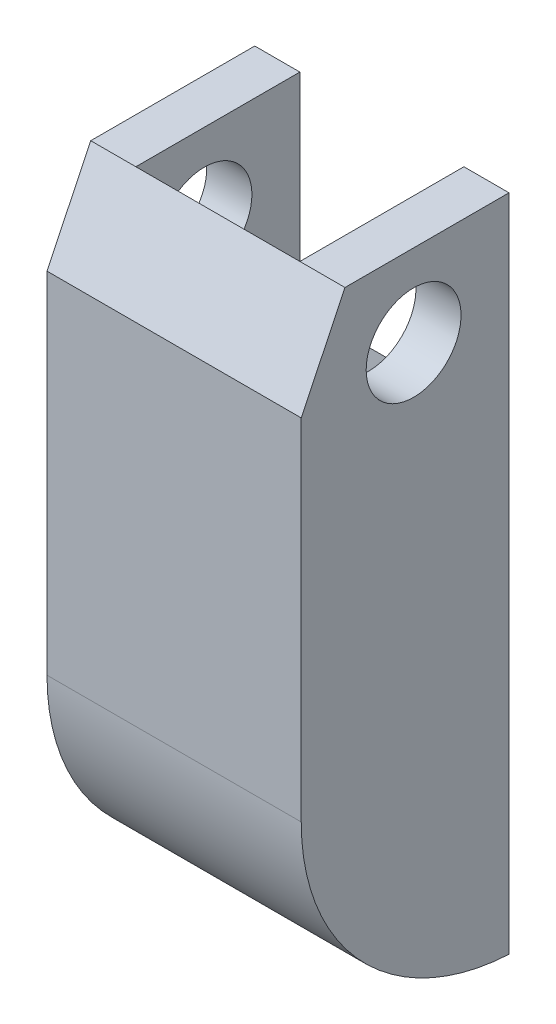
SolidWorks part; units mm, degrees
ref_plane "Front Plane" through (0, 0, 0) normal (0, 0, 1) x (1, 0, 0)
ref_plane "Top Plane" through (0, 0, 0) normal (0, 1, 0) x (1, 0, 0)
ref_plane "Right Plane" through (0, 0, 0) normal (1, 0, 0) x (0, 0, -1)
sketch "Sketch1" plane through (0, 0, 0) normal (0, 0, 1) x (1, 0, 0)
  line L1 (0, 0) -> (11.811, 0)
  line L2 (0, 0) -> (0, 45.9892)
  line L3 (0, 45.9892) -> (11.811, 45.9892)
  line L4 (11.811, 0) -> (11.811, 45.9892)
  dimension "D1" = 11.811
  dimension "D2" = 45.9892
extrude "Boss-Extrude1" add sketch "Sketch1" along normal blind 9.652 contours L2 L3 L4 L1
fillet "Fillet5" radius 4.826 1 edges at (5.9055, 45.9892, 0)
sketch "Sketch2" plane through (0, 0, 0) normal (0, 0, -1) x (-1, 0, 0)
  line L0 (0, 45.9892) -> (-11.811, 45.9892) construction
  line L1 (-9.7155, 45.9892) -> (-2.0955, 45.9892)
  line L2 (-9.7155, 45.9892) -> (-9.7155, 23.6372)
  line L3 (-9.7155, 23.6372) -> (-2.0955, 23.6372)
  line L4 (-2.0955, 45.9892) -> (-2.0955, 23.6372)
  line L5 (0, 0) -> (0, 41.1632) construction
  dimension "D1" = 22.352
  dimension "D2" = 7.62
  dimension "D3" = 2.0955
extrude "Cut-Extrude1" cut sketch "Sketch2" against normal blind 7.62
sketch "Sketch3" plane through (0, 0, 0) normal (-1, 0, 0) x (0, 0, 1)
  line L0 (7.62, 45.9892) -> (7.62, 23.6372) construction
  line L2 (7.62, 23.6372) -> (0, 23.6372) construction
  circle A0 centre (4.4323, 26.8249) radius 2.2035
  dimension "D1" = 3.1877
  dimension "D3" = 4.4069
  dimension "D2" = 3.1877
extrude "Cut-Extrude2" cut sketch "Sketch3" against normal through all and the other way through all
fillet "Fillet4" radius 4.826 1 edges at (5.9055, 45.9892, 9.652)
fillet "Fillet6" radius 10.16 1 edges at (5.9055, 0, 9.652)
sketch "Sketch4" plane through (11.811, 0, 0) normal (1, 0, 0) x (0, 0, -1)
  line L0 (-9.652, 26.4038) -> (-7.62, 30.6349)
  line L1 (-9.652, 10.1473) -> (-9.652, 41.1632) construction
  line L2 (-7.62, 30.6349) -> (0, 30.6349)
  line L3 (0, 0) -> (0, 41.1632) construction
  line L4 (-9.652, 26.4038) -> (-9.652, 45.9892)
  line L5 (-9.652, 45.9892) -> (0, 45.9892)
  line L6 (0, 45.9892) -> (0, 30.6349)
  line L7 (-0.4369, 28.7437) -> (4.2626, 18.9582) construction
  line L8 (-4.4323, 26.8249) -> (0, 26.8249) construction
  line L9 (-4.4323, 26.8249) -> (-0.4369, 28.7437) construction
  line L10 (-4.4323, 26.8249) -> (-0.4369, 24.9061) construction
  arc A0 (-4.826, 45.9892) -> (-9.652, 41.1632) centre (-4.826, 41.1632) ccw construction
  circle A1 centre (7.1247, 20.3327) radius 3.175 construction
  point P14 (-4.4323, 26.8249)
  point P22 (0, 0)
  point P23 (0, 0)
  dimension "D2" = 6.35
  dimension "D1" = 3.81
  dimension "D3" = 11.557
  dimension "D4" = 6.4922
extrude "Cut-Extrude3" cut sketch "Sketch4" against normal through all
sketch "Sketch5" plane through (9.7155, 0, 0) normal (-1, 0, 0) x (0, 0, 1)
  line L0 (5.1581, 23.6372) -> (0, 21.1601)
  line L1 (0, 21.1601) -> (0, 23.6372)
  line L2 (0, 23.6372) -> (5.1581, 23.6372)
  line L3 (4.4323, 26.8249) -> (0.4369, 24.9061) construction
  line L4 (4.4323, 26.8249) -> (7.62, 26.8249) construction
  line L5 (4.4323, 26.8249) -> (5.8123, 23.9514) construction
  line L6 (7.62, 30.6349) -> (7.62, 23.6372) construction
  line L7 (5.8123, 23.9514) -> (5.1581, 23.6372)
  line L8 (7.62, 26.8249) -> (7.62, 23.6372)
  line L9 (7.62, 23.6372) -> (5.1581, 23.6372)
  arc A0 (5.8123, 23.9514) -> (7.62, 26.8249) centre (4.4323, 26.8249) ccw
  point P2 (7.62, 26.845)
  point P13 (0, 0)
  line M4 (7.62, 23.6372) -> (7.62, 30.6349)
  line M7 (0, 23.6372) -> (7.62, 23.6372)
extrude "Cut-Extrude4" cut sketch "Sketch5" along normal up to surface (7.62 mm away) contours L1 L0 M7 region at (9.7155, 22.8115, 1.7194) up to face at (2.0955, 24.6215, 4.4323)
extrude "Boss-Extrude2" add sketch "Sketch5<3>" along normal up to surface (7.62 mm away) contours A0 L7 M7 M4 region at (9.7155, 24.361, 6.9399) up to face at (2.0955, 24.6215, 4.4323)
sketch "Sketch5<3>" plane through (9.7155, 0, 0) normal (-1, 0, 0) x (0, 0, 1) same geometry as "Sketch5"
